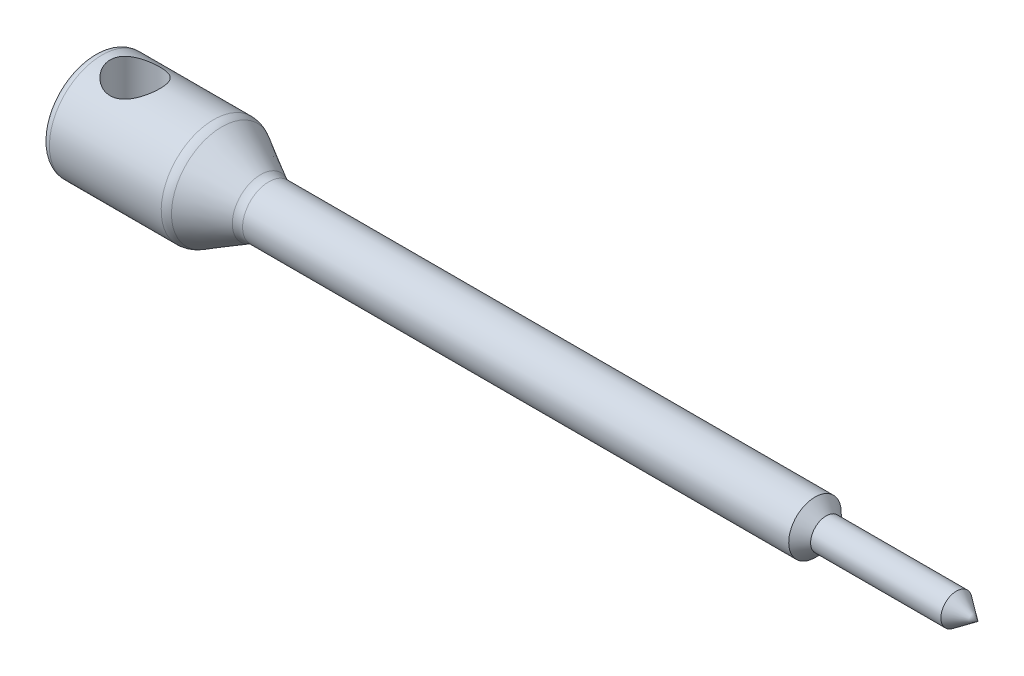
SolidWorks part; units mm, degrees
ref_plane "Front Plane" through (0, 0, 0) normal (0, 0, 1) x (1, 0, 0)
ref_plane "Top Plane" through (0, 0, 0) normal (0, 1, 0) x (1, 0, 0)
ref_plane "Right Plane" through (0, 0, 0) normal (1, 0, 0) x (0, 0, -1)
sketch "Sketch1" plane through (0, 0, 0) normal (0, 0, 1) x (1, 0, 0)
  line L0 (0, 0) -> (0, 6.325)
  line L1 (0, 6.325) -> (15, 6.325)
  line L2 (15, 6.325) -> (20.6, 3.165)
  line L3 (20.6, 3.165) -> (86.95, 3.165)
  line L4 (86.95, 3.165) -> (88.3, 1.875)
  line L5 (88.3, 1.875) -> (104, 1.875)
  line L6 (106.6, 0) -> (0, 0) construction
  line L7 (104, 1.875) -> (106.6, 0)
  line L8 (0, 0) -> (106.6, 0)
  dimension "D1" = 1.875
  dimension "D2" = 2.6
  dimension "D3" = 18.3
  dimension "D4" = 3.165
  dimension "D5" = 19.65
  dimension "D6" = 6.325
  dimension "D7" = 86
  dimension "D8" = 15
  dimension "D9" = 106.6
revolve "Revolve1" add sketch "Sketch1" angle 360 about L6
sketch "Sketch2" plane through (0, 0, 0) normal (0, 1, 0) x (1, 0, 0)
  line L0 (0, 0) -> (5, 0) construction
  circle A0 centre (5, 0) radius 3
  dimension "D1" = 6
  dimension "D2" = 5
extrude "Cut-Extrude1" cut sketch "Sketch2" against normal blind 10 and the other way blind 10
fillet "Fillet1" radius 1 1 edges at (0, 6.325, 0)
fillet "Fillet2" radius 2 2 edges at (20.6, 3.165, 0) (15, 6.325, 0)
sketch "Sketch3" plane through (0, 0, 0) normal (-1, 0, 0) x (0, 0, 1)
  circle A0 centre (0, 0) radius 1.5
  dimension "D1" = 3
extrude "Cut-Extrude2" cut sketch "Sketch3" against normal blind 6
sketch "Sketch4" plane through (0, 0, 0) normal (0, 1, 0) x (1, 0, 0)
  line L0 (5, 0) -> (106.6, 0) construction
  line L1 (104, -1.875) -> (106.6, 0) construction
